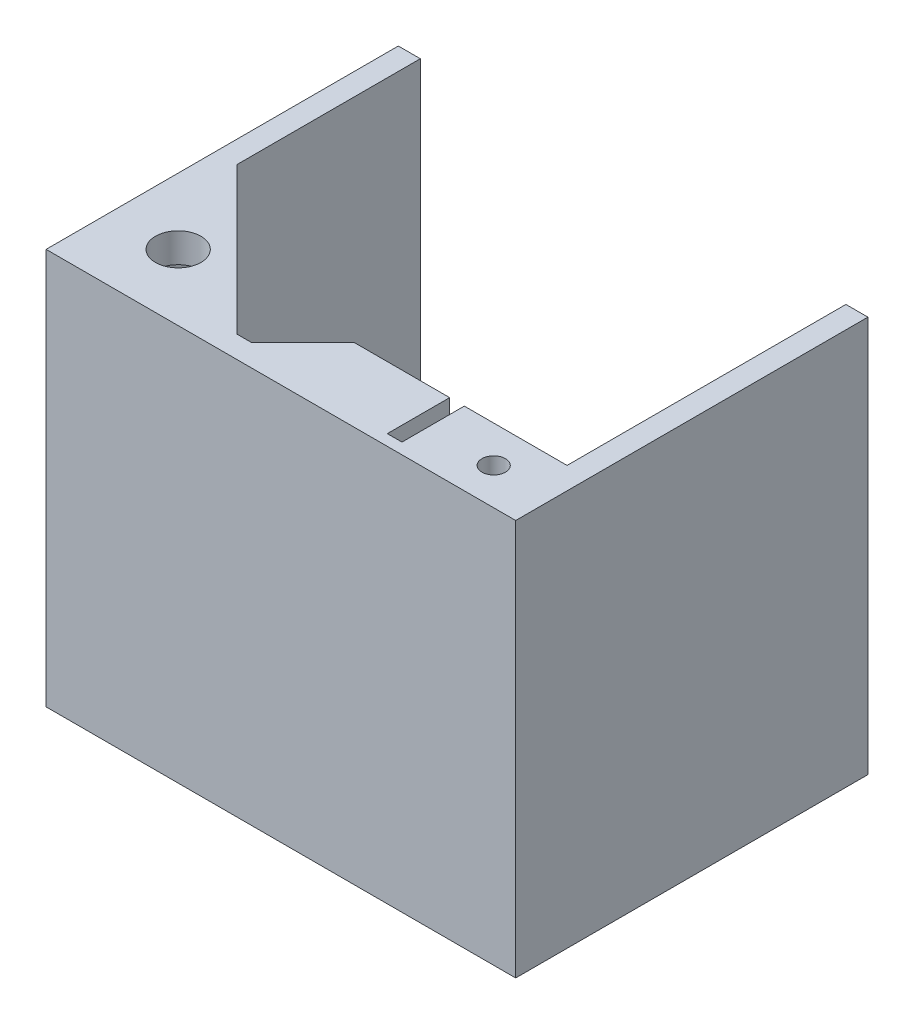
SolidWorks part; units mm, degrees
ref_plane "Płaszczyzna przednia" through (0, 0, 0) normal (0, 0, 1) x (1, 0, 0)
ref_plane "Płaszczyzna górna" through (0, 0, 0) normal (0, 1, 0) x (1, 0, 0)
ref_plane "Płaszczyzna prawa" through (0, 0, 0) normal (1, 0, 0) x (0, 0, -1)
sketch "Sketch1" plane through (0, 0, 0) normal (0, 1, 0) x (1, 0, 0)
  line L1 (-32, 24) -> (32, 24)
  line L2 (-32, 24) -> (-32, -24)
  line L3 (-32, -24) -> (32, -24)
  line L4 (32, 24) -> (32, -24)
  line L5 (-32, 24) -> (32, -24) construction
  line L6 (-32, -24) -> (32, 24) construction
  point P0 (0, 0)
  dimension "D1" = 64
  dimension "D2" = 48
extrude "Boss-Extrude1" add sketch "Sketch1" along normal blind 4
sketch "Sketch2" plane through (0, 0, 0) normal (0, -1, 0) x (1, 0, 0)
  line L9 (-20.8246, -16) -> (-22.4123, -13.25)
  line L10 (-22.4123, -13.25) -> (-25.5877, -13.25)
  line L11 (-25.5877, -13.25) -> (-27.1754, -16)
  line L12 (-27.1754, -16) -> (-25.5877, -18.75)
  line L13 (-25.5877, -18.75) -> (-22.4123, -18.75)
  line L14 (-22.4123, -18.75) -> (-20.8246, -16)
  line L15 (-32, -24) -> (-32, 24) construction
  line L16 (32, -24) -> (-32, -24) construction
  circle A0 centre (-24, -16) radius 2.75 construction
  dimension "D1" = 8
  dimension "D2" = 8
extrude "Cut-Extrude1" cut sketch "Sketch2" against normal blind 2.4
sketch "Sketch4" plane through (0, 0, 0) normal (0, -1, 0) x (1, 0, 0)
  line L0 (-32, -24) -> (-32, 24) construction
  line L1 (9.1754, 10) -> (7.5877, 12.75)
  line L2 (7.5877, 12.75) -> (4.4123, 12.75)
  line L3 (4.4123, 12.75) -> (2.8246, 10)
  line L4 (2.8246, 10) -> (4.4123, 7.25)
  line L5 (4.4123, 7.25) -> (7.5877, 7.25)
  line L6 (7.5877, 7.25) -> (9.1754, 10)
  line L8 (32, -24) -> (-32, -24) construction
  circle A0 centre (6, 10) radius 2.75 construction
  dimension "D1" = 38
  dimension "D2" = 34
extrude "Cut-Extrude2" cut sketch "Sketch4" against normal blind 2.4
sketch "Sketch6" plane through (0, 4, 0) normal (0, 1, 0) x (1, 0, 0)
  line L0 (-29, 21) -> (-29, 24)
  line L1 (-32, 24) -> (32, 24)
  line L2 (-32, 24) -> (-32, -24)
  line L3 (-32, -24) -> (32, -24)
  line L4 (32, 24) -> (32, -24)
  line L5 (-29, 21) -> (29, 21)
  line L6 (-29, 21) -> (-29, -21)
  line L7 (-29, -21) -> (29, -21)
  line L8 (29, 21) -> (29, -21)
  line L9 (-29, 21) -> (29, -21) construction
  line L10 (-29, -21) -> (29, 21) construction
  line L11 (29, 21) -> (29, 24)
  point P6 (0, 0)
  line M1 (32, -24) -> (32, 24)
  line M2 (32, 24) -> (-32, 24)
  line M3 (-32, 24) -> (-32, -24)
  line M4 (-32, -24) -> (32, -24)
  dimension "D1" = 58
  dimension "D2" = 42
extrude "Boss-Extrude3" add sketch "Sketch6" along normal blind 50 contours L11 L8 L7 L6 L0 M2 M3 M4 M1 region at (-29.8, 4, 0)
sketch "Sketch9" plane through (0, 4, 0) normal (0, 1, 0) x (1, 0, 0)
  line L0 (1, -13) -> (-7, -21)
  line L3 (29, -13) -> (1, -13)
  line L5 (-29, -21) -> (29, -21) construction
  line L6 (-7, -21) -> (29, -21)
  line L7 (1, -13) -> (-7, -21)
  line L9 (29, -21) -> (29, -13)
  line M3 (29, -21) -> (29, 24)
  line M6 (-29, -21) -> (29, -21)
  dimension "D1" = 8
  dimension "D2" = 8
  dimension "D3" = 28
extrude "Boss-Extrude4" add sketch "Sketch9" along normal blind 50 contours L3 L0 M3 M6 region at (12.9167, 4, 17.1667)
sketch "Sketch10" plane through (0, 0, 13) normal (0, 0, -1) x (-1, 0, 0)
  line L0 (-29, 54) -> (-29, 4) construction
  line L1 (-27, 39) -> (-1, 39)
  line L2 (-27, 39) -> (-27, 13)
  line L3 (-27, 13) -> (-1, 13)
  line L4 (-1, 39) -> (-1, 13)
  line L5 (-27, 39) -> (-1, 13) construction
  line L6 (-27, 13) -> (-1, 39) construction
  line L7 (-14, 39) -> (-14, 54) construction
  line L9 (-29, 54) -> (-1, 54) construction
  line L15 (-14.9986, 39) -> (-13.0014, 39)
  line L16 (-14.9986, 39) -> (-14.9986, 54)
  line L17 (-14.9986, 54) -> (-13.0014, 54)
  line L18 (-13.0014, 39) -> (-13.0014, 54)
  line L19 (-14.9986, 39) -> (-13.0014, 54) construction
  line L20 (-14.9986, 54) -> (-13.0014, 39) construction
  point P0 (-14, 26)
  point P9 (-14, 46.5)
  line M4 (-1, 4) -> (-1, 54)
  line M5 (-1, 54) -> (-29, 54)
  dimension "D1" = 26
  dimension "D2" = 26
  dimension "D3" = 15
  dimension "D5" = 28
extrude "Cut-Extrude4" cut sketch "Sketch10" against normal blind 9.5 contours L2 L3 L1 M4 | L1 M5 region at (14, 26, 13) region at (14, 46.5, 13)
sketch "Sketch13" plane through (0, 54, 0) normal (0, 1, 0) x (1, 0, 0)
  line L1 (29, -13) -> (-7.9463, -13)
  line L2 (29, -13) -> (29, -14)
  line L3 (29, -14) -> (-7.9463, -14)
  line L4 (-7.9463, -13) -> (-7.9463, -14)
  dimension "D1" = 1
extrude "Cut-Extrude6" cut sketch "Sketch13" against normal blind 32
sketch "Sketch15" plane through (0, 54, 0) normal (0, 1, 0) x (1, 0, 0)
  line L0 (-29, -1) -> (-9, -21)
  line L5 (-29, 24) -> (-29, -21) construction
  line L6 (-29, -21) -> (-7, -21) construction
  line L7 (-29, 24) -> (-29, -21) construction
  line L8 (-29, -1) -> (-29, -21)
  line L9 (-29, -21) -> (-9, -21)
  line L10 (-32, 24) -> (-32, -24) construction
  line L11 (-32, -24) -> (32, -24) construction
  circle A0 centre (-23, -15) radius 3.1
  dimension "D3" = 9
  dimension "D1" = 20
  dimension "D2" = 20
  dimension "D4" = 9
extrude "Boss-Extrude5" add sketch "Sketch15" against normal blind 4
sketch "Sketch17" plane through (0, 54, 0) normal (0, 1, 0) x (1, 0, 0)
  line L0 (32, -24) -> (32, 24) construction
  line L7 (-32, -24) -> (32, -24) construction
  line L8 (24, -19) -> (24, -24) construction
  line L9 (24, -19) -> (32, -19) construction
  line L11 (24, -15.8246) -> (21.25, -17.4123)
  line L12 (21.25, -17.4123) -> (21.25, -20.5877)
  line L13 (21.25, -20.5877) -> (24, -22.1754)
  line L14 (24, -22.1754) -> (26.75, -20.5877)
  line L15 (26.75, -20.5877) -> (26.75, -17.4123)
  line L16 (26.75, -17.4123) -> (24, -15.8246)
  circle A0 centre (24, -19) radius 2.75 construction
  dimension "D1" = 8
  dimension "D2" = 5
extrude "Cut-Extrude7" cut sketch "Sketch17" against normal blind 7
sketch "Sketch18" plane through (0, 0, 14) normal (0, 0, -1) x (-1, 0, 0)
  line L0 (-14.9986, 54) -> (-29, 54) construction
  line L1 (-26.8, 49.5) -> (-21.2, 49.5)
  line L2 (-26.8, 49.5) -> (-26.8, 47)
  line L3 (-26.8, 47) -> (-21.2, 47)
  line L4 (-21.2, 49.5) -> (-21.2, 47)
  line L5 (-32, 54) -> (-32, 0) construction
  point P6 (-24, 49.5)
  dimension "D1" = 7
  dimension "D2" = 2.5
  dimension "D3" = 5.6
  dimension "D4" = 8
extrude "Cut-Extrude8" cut sketch "Sketch18" against normal blind 5
sketch "Sketch19" plane through (0, 54, 0) normal (0, 1, 0) x (1, 0, 0)
  line L0 (24, -22.1754) -> (24, -15.8246) construction
  line L5 (26.75, -17.4123) -> (24, -15.8246) construction
  line L6 (24, -15.8246) -> (26.75, -19) construction
  line L7 (26.75, -20.5877) -> (26.75, -17.4123) construction
  line L8 (26.75, -19) -> (21.25, -19) construction
  line L10 (20.7023, -15.4012) -> (27.2977, -15.4012)
  line L11 (20.7023, -15.4012) -> (20.7023, -22.5988)
  line L12 (20.7023, -22.5988) -> (27.2977, -22.5988)
  line L13 (27.2977, -15.4012) -> (27.2977, -22.5988)
  line L14 (20.7023, -15.4012) -> (27.2977, -22.5988) construction
  line L15 (20.7023, -22.5988) -> (27.2977, -15.4012) construction
  circle A0 centre (24, -19) radius 1.6
extrude "Boss-Extrude8" add sketch "Sketch19" against normal blind 4.5
fillet "Fillet1" radius 1.5 2 edges at (-29, 50, 11) (-19, 50, 21)
